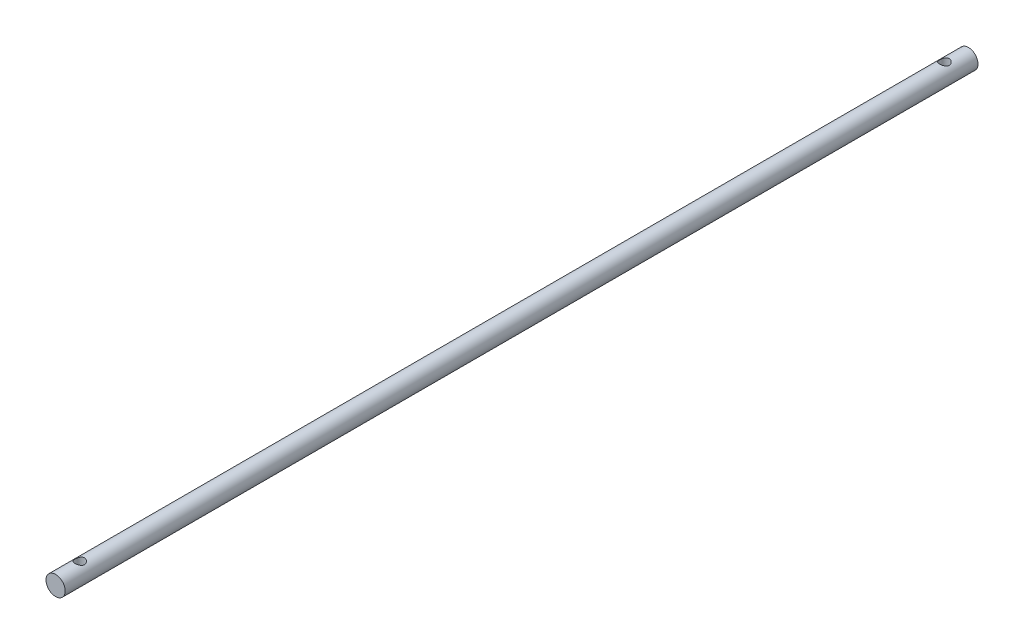
SolidWorks part; units mm, degrees
material "Plain Carbon Steel"
ref_plane "Front Plane" through (0, 0, 0) normal (0, 0, 1) x (1, 0, 0)
ref_plane "Top Plane" through (0, 0, 0) normal (0, 1, 0) x (1, 0, 0)
ref_plane "Right Plane" through (0, 0, 0) normal (1, 0, 0) x (0, 0, -1)
sketch "Sketch1" plane through (0, 0, 0) normal (0, 0, 1) x (1, 0, 0)
  circle A0 centre (0, 0) radius 4
extrude "Extrude1" add sketch "Sketch1" along normal blind 380
hole_wizard "Ø4.0 (4) Diameter Hole1" positions "Sketch4" profile "Sketch3" hole size "Ø4.0" standard "Ansi Metric" end condition through all
sketch "Sketch4" plane through (0, 0, 0) normal (0, 1, 0) x (1, 0, 0)
  line L0 (4, 0) -> (-4, 0) construction
  line L1 (-4, -380) -> (4, -380) construction
  point P1 (0, -10)
  point P3 (0, -370)
  dimension "D1" = 10
  dimension "D2" = 10
sketch "Sketch3" plane through (0, 0, 10) normal (1, 0, 0) x (0, 0, -1)
  line L0 (0, 0) -> (0, 4)
  line L1 (0, 4) -> (2, 4)
  line L2 (2, 4) -> (2, 0)
  line L5 (2, 0) -> (0, 0)
  line L11 (0, -6.35) -> (0, 107.95) construction
  dimension "Thru Hole Dia." = 4
  dimension "Thru Hole Depth" = 4
